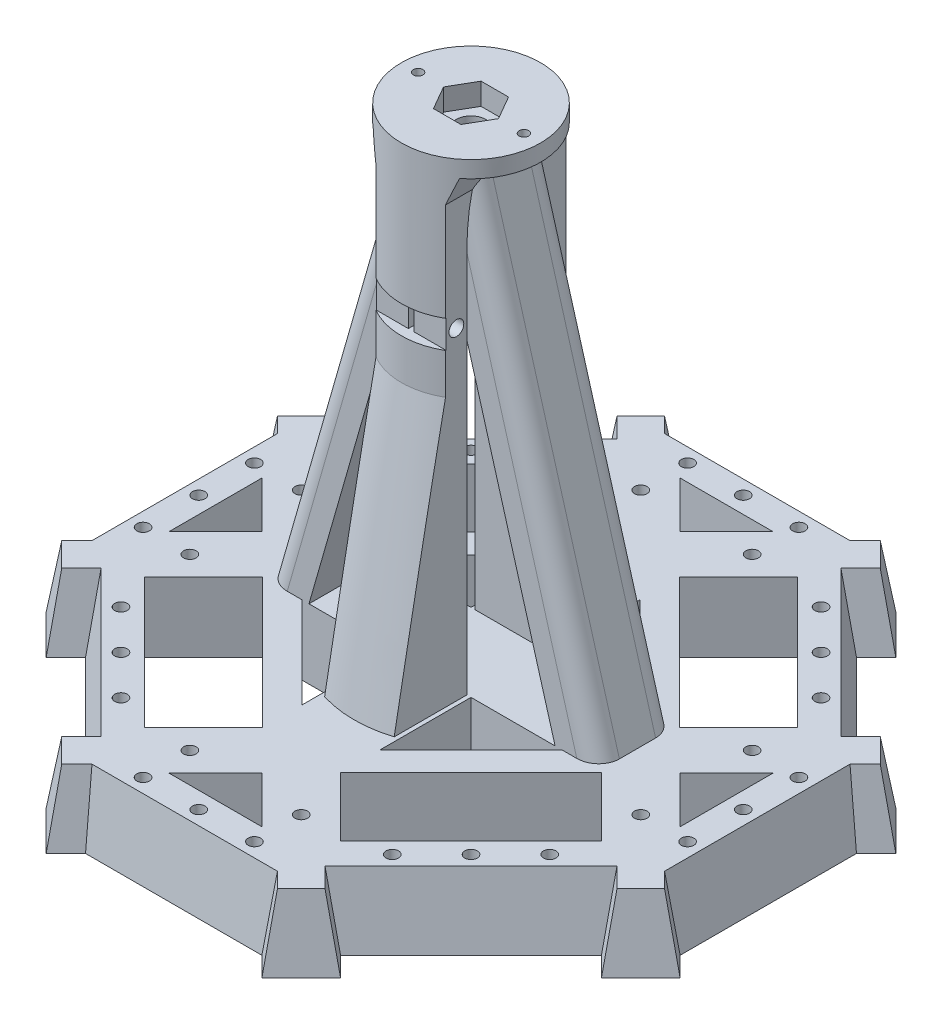
SolidWorks part; units mm, degrees
ref_plane "Front Plane" through (0, 0, 0) normal (0, 0, 1) x (1, 0, 0)
ref_plane "Top Plane" through (0, 0, 0) normal (0, 1, 0) x (1, 0, 0)
ref_plane "Right Plane" through (0, 0, 0) normal (1, 0, 0) x (0, 0, -1)
sketch "Sketch1" plane through (0, 0, 0) normal (0, 1, 0) x (1, 0, 0)
  line L0 (-1000, 0) -> (49000, 0) construction
  line L1 (-12.5, 29) -> (12.5, 29)
  line L2 (-12.5, 29) -> (-12.5, 14)
  line L3 (-12.5, 14) -> (12.5, 14)
  line L4 (12.5, 29) -> (12.5, 14)
  line L5 (-12.5, 29) -> (12.5, 14) construction
  line L6 (-12.5, 14) -> (12.5, 29) construction
  line L7 (-12.5, -14) -> (12.5, -29) construction
  line L8 (-12.5, -29) -> (12.5, -14) construction
  line L9 (12.5, -29) -> (12.5, -14)
  line L10 (-12.5, -14) -> (12.5, -14)
  line L11 (-12.5, -29) -> (-12.5, -14)
  line L12 (-12.5, -29) -> (12.5, -29)
  point P0 (0, 21.5)
  point P12 (0, -21.5)
  dimension "D1" = 25
  dimension "D2" = 15
  dimension "D3" = 14
extrude "Boss-Extrude1" add sketch "Sketch1" along normal blind 250
sketch "Sketch3" plane through (0, 0, 29) normal (0, 0, 1) x (1, 0, 0)
  line L0 (-12.5, 250) -> (-4.8, 276.4)
  line L1 (4.8, 276.4) -> (12.5, 250)
  line L2 (-12.5, 250) -> (12.5, 250) construction
  line L3 (-12.5, 250) -> (12.5, 250)
  arc A0 (4.8, 276.4) -> (-4.8, 276.4) centre (0, 275) ccw
  dimension "D1" = 10
  dimension "D2" = 25
extrude "Boss-Extrude2" add sketch "Sketch3" against normal up to surface (58 mm away) up to face at (0, 125, -29)
sketch "Sketch4" plane through (0, 250, 0) normal (0, -1, 0) x (1, 0, 0)
  line L1 (-12.5, 14) -> (12.5, 14)
  line L2 (-12.5, 14) -> (-12.5, -14)
  line L3 (-12.5, -14) -> (12.5, -14)
  line L4 (12.5, 14) -> (12.5, -14)
extrude "Cut-Extrude2" cut sketch "Sketch4" against normal through all
sketch "Sketch5" plane through (0, 0, -29) normal (0, 0, -1) x (-1, 0, 0)
  circle A1 centre (0, 275) radius 5
  dimension "D1" = 10
extrude "Boss-Extrude3" add sketch "Sketch5" against normal up to surface (58 mm away) up to face at (0, 176.0667, 29)
sketch "Sketch6" plane through (0, 0, 0) normal (0, -1, 0) x (1, 0, 0)
  line L1 (-12.5, -100) -> (12.5, -100)
  line L2 (-12.5, -100) -> (-12.5, 100)
  line L3 (-12.5, 100) -> (12.5, 100)
  line L4 (12.5, -100) -> (12.5, 100)
  line L5 (-12.5, -100) -> (12.5, 100) construction
  line L6 (-12.5, 100) -> (12.5, -100) construction
  point P0 (0, 0)
  dimension "D1" = 25
  dimension "D2" = 200
extrude "Boss-Extrude4" add sketch "Sketch6" along normal blind 25
sketch "Sketch7" plane through (0, 0, 0) normal (0, 1, 0) x (1, 0, 0)
  line L1 (-12.5, -14) -> (12.5, -14)
  line L2 (-12.5, -14) -> (-12.5, 14)
  line L3 (-12.5, 14) -> (12.5, 14)
  line L4 (12.5, -14) -> (12.5, 14)
extrude "Cut-Extrude3" cut sketch "Sketch7" along normal blind 323
sketch "Sketch12" plane through (0, 0, 0) normal (0, 1, 0) x (1, 0, 0)
  line L0 (-1000, 0) -> (49000, 0) construction
  line L1 (26.5, 39) -> (112.5, 39)
  line L4 (112.5, 39) -> (112.5, 14)
  line L5 (0, -1000) -> (0, 49000) construction
  line L6 (-12.5, 39) -> (-12.5, 14)
  line L7 (-26.5, 39) -> (-112.5, 39)
  line L8 (-112.5, 39) -> (-112.5, 14)
  line L9 (-26.5, 14) -> (-112.5, 14)
  line L10 (112.5, -39) -> (112.5, -14)
  line L13 (26.5, -39) -> (112.5, -39)
  line L14 (-26.5, -14) -> (-112.5, -14)
  line L15 (-112.5, -39) -> (-112.5, -14)
  line L16 (-26.5, -39) -> (-112.5, -39)
  line L17 (-12.5, -39) -> (-12.5, -14)
  line L18 (12.5, -75) -> (12.5, -100)
  line L21 (-12.5, 100) -> (12.5, 100) construction
  line L22 (12.5, 75) -> (12.5, 100) construction
  line L23 (-12.5, -100) -> (12.5, -100)
  line L24 (-12.5, -75) -> (-12.5, -100)
  line L25 (-12.5, -75) -> (12.5, -75)
  line L26 (-887.5, 26.5) -> (49112.5, 26.5) construction
  line L27 (-12.5, -14) -> (-12.5, 14) construction
  line L33 (-12.5, 14) -> (-12.5, 0)
  line L35 (-12.5, 53) -> (-12.5, 39)
  line L36 (-12.5, -100) -> (-12.5, -29) construction
  line L37 (-12.5, -53) -> (-12.5, -39)
  line L38 (12.5, -29) -> (12.5, -100) construction
  line L39 (12.5, 100) -> (12.5, 29) construction
  line L56 (12.5, 53) -> (12.5, 14)
  line L57 (112.5, 14) -> (12.5, 14)
  line L59 (112.5, -14) -> (12.5, -14)
  line L61 (12.5, -14) -> (12.5, -53)
  line L62 (-26.5, -14) -> (-12.5, -14)
  circle A0 centre (25, 26.5) radius 2.4
  circle A1 centre (37.5, 26.5) radius 2.4
  circle A2 centre (50, 26.5) radius 2.4
  circle A3 centre (62.5, 26.5) radius 2.4
  circle A4 centre (75, 26.5) radius 2.4
  circle A5 centre (87.5, 26.5) radius 2.4
  circle A6 centre (100, 26.5) radius 2.4
  circle A7 centre (100, -26.5) radius 2.4
  circle A8 centre (87.5, -26.5) radius 2.4
  circle A9 centre (75, -26.5) radius 2.4
  circle A10 centre (62.5, -26.5) radius 2.4
  circle A11 centre (50, -26.5) radius 2.4
  circle A12 centre (37.5, -26.5) radius 2.4
  circle A13 centre (25, -26.5) radius 2.4
  circle A14 centre (-100, 26.5) radius 2.4
  circle A15 centre (-87.5, 26.5) radius 2.4
  circle A16 centre (-75, 26.5) radius 2.4
  circle A17 centre (-62.5, 26.5) radius 2.4
  circle A18 centre (-50, 26.5) radius 2.4
  circle A19 centre (-37.5, 26.5) radius 2.4
  circle A20 centre (-25, 26.5) radius 2.4
  circle A21 centre (-25, -26.5) radius 2.4
  circle A22 centre (-37.5, -26.5) radius 2.4
  circle A23 centre (-50, -26.5) radius 2.4
  circle A24 centre (-62.5, -26.5) radius 2.4
  circle A25 centre (-75, -26.5) radius 2.4
  circle A26 centre (-87.5, -26.5) radius 2.4
  circle A27 centre (-100, -26.5) radius 2.4
  circle A28 centre (0, 90) radius 2.4
  circle A29 centre (0, 85) radius 2.4
  circle A30 centre (0, -90) radius 2.4
  circle A31 centre (0, -85) radius 2.4
  arc A35 (-26.5, 14) -> (-12.5, 0) centre (-26.5, 0) cw
  arc A36 (-26.5, 39) -> (-12.5, 53) centre (-26.5, 53) ccw
  arc A37 (-26.5, -39) -> (-12.5, -53) centre (-26.5, -53) cw
  arc A38 (12.5, -53) -> (26.5, -39) centre (26.5, -53) cw
  arc A39 (12.5, 53) -> (26.5, 39) centre (26.5, 53) ccw
  point P34 (112.5, 26.5)
  dimension "D5" = 4.8
  dimension "D8" = 12.5
  dimension "D9" = 4.8
  dimension "D10" = 4.8
  dimension "D11" = 10
  dimension "D14" = 14
  dimension "D15" = 14
  dimension "D16" = 14
  dimension "D17" = 14
  dimension "D18" = 14
  dimension "D1" = 25
  dimension "D3" = 61
  dimension "D4" = 25
  dimension "D7" = 7
extrude "Boss-Extrude7" add sketch "Sketch12" against normal up to surface (25 mm away) up to face at (0, -25, 0)
ref_plane "Plane1" through (-0.9497, -3.312, 0) normal (0.2756, 0.9613, 0) x (0, 0, -1)
sketch "Sketch14" plane through (-0.9497, -3.312, 0) normal (0.2756, 0.9613, 0) x (0, 0, -1)
  line L0 (14, 56.8936) -> (14, -12.0158) construction
  line L1 (-14, 57.5) -> (14, 57.5)
  line L2 (-14, 57.5) -> (-14, 42.5)
  line L3 (-14, 42.5) -> (14, 42.5)
  line L4 (14, 57.5) -> (14, 42.5)
  line L5 (-14, 57.5) -> (14, 42.5) construction
  line L6 (-14, 42.5) -> (14, 57.5) construction
  point P0 (0, 50)
  dimension "D1" = 28
  dimension "D2" = 15
  dimension "D3" = 50
sketch "Sketch16" plane through (0, 0, 0) normal (0, 1, 0) x (1, 0, 0)
  line L1 (12.5, -88.0748) -> (97.5, -39)
  line L2 (12.5, -70.7543) -> (67.5, -39)
  line L4 (12.5, -53) -> (12.5, -100) construction
  line L5 (-12.5, -70.7543) -> (-12.5, -88.0748)
  line L6 (26.5, -39) -> (112.5, -39) construction
  line L7 (112.5, -39) -> (112.5, -14) construction
  line L8 (-97.5, -39) -> (-67.5, -39)
  line L9 (97.5, -39) -> (67.5, -39)
  line L11 (12.5, -70.7543) -> (12.5, -88.0748)
  line L12 (-1000, 0) -> (49000, 0) construction
  line L13 (0, -1000) -> (0, 49000) construction
  line L14 (-834.739, -568.5682) -> (42466.5312, 24431.4318) construction
  line L15 (-12.5, -70.7543) -> (-67.5, -39)
  line L16 (-12.5, -88.0748) -> (-97.5, -39)
  line L17 (-12.5, 88.0748) -> (-97.5, 39)
  line L18 (-12.5, 70.7543) -> (-67.5, 39)
  line L19 (-97.5, 39) -> (-67.5, 39)
  line L20 (-12.5, 70.7543) -> (-12.5, 88.0748)
  line L21 (12.5, 70.7543) -> (12.5, 88.0748)
  line L22 (97.5, 39) -> (67.5, 39)
  line L23 (12.5, 70.7543) -> (67.5, 39)
  line L24 (12.5, 88.0748) -> (97.5, 39)
  circle A0 centre (25, -72.1976) radius 2.4
  circle A1 centre (37.5, -64.9808) radius 2.4
  circle A2 centre (50, -57.7639) radius 2.4
  circle A3 centre (75, -43.3301) radius 2.4
  circle A4 centre (62.5, -50.547) radius 2.4
  circle A5 centre (-62.5, -50.547) radius 2.4
  circle A6 centre (-75, -43.3301) radius 2.4
  circle A7 centre (-50, -57.7639) radius 2.4
  circle A8 centre (-37.5, -64.9808) radius 2.4
  circle A9 centre (-25, -72.1976) radius 2.4
  circle A10 centre (-25, 72.1976) radius 2.4
  circle A11 centre (-37.5, 64.9808) radius 2.4
  circle A12 centre (-50, 57.7639) radius 2.4
  circle A13 centre (-75, 43.3301) radius 2.4
  circle A14 centre (-62.5, 50.547) radius 2.4
  circle A15 centre (62.5, 50.547) radius 2.4
  circle A16 centre (75, 43.3301) radius 2.4
  circle A17 centre (50, 57.7639) radius 2.4
  circle A18 centre (37.5, 64.9808) radius 2.4
  circle A19 centre (25, 72.1976) radius 2.4
  point P16 (12.5, -79.4145)
  point P20 (25, -26.5)
  point P21 (50, -26.5)
  point P23 (62.5, -26.5)
  point P24 (75, -26.5)
  point P38 (37.5, -26.5)
  dimension "D1" = 4.8
  dimension "D2" = 30
  dimension "D3" = 15
extrude "Boss-Extrude13" add sketch "Sketch16" against normal up to surface (25 mm away) up to face at (-0.944, -25, -0.116)
extrude "Boss-Extrude14" add sketch "Sketch14" along normal blind 215 and the other way blind 48
mirror "Mirror1" about plane through (0, 0, 0) normal (1, 0, 0) of "Boss-Extrude14"
sketch "Sketch24" plane through (0, -25, 0) normal (0, -1, 0) x (1, 0, 0)
  line L1 (-207.1011, -152.3344) -> (207.1011, -152.3344)
  line L2 (-207.1011, -152.3344) -> (-207.1011, 152.3344)
  line L3 (-207.1011, 152.3344) -> (207.1011, 152.3344)
  line L4 (207.1011, -152.3344) -> (207.1011, 152.3344)
  line L5 (-207.1011, -152.3344) -> (207.1011, 152.3344) construction
  line L6 (-207.1011, 152.3344) -> (207.1011, -152.3344) construction
  point P0 (0, 0)
extrude "Cut-Extrude9" cut sketch "Sketch24" along normal blind 165
sketch "Sketch25" plane through (0, 0, -29) normal (0, 0, -1) x (-1, 0, 0)
  line L0 (-12.5, 0) -> (12.5, 0) construction
  line L1 (-74.6681, 165) -> (102.6778, 165)
  line L2 (-74.6681, 165) -> (-74.6681, 358.0748)
  line L3 (-74.6681, 358.0748) -> (102.6778, 358.0748)
  line L4 (102.6778, 165) -> (102.6778, 358.0748)
  dimension "D1" = 165
extrude "Cut-Extrude10" cut sketch "Sketch25" against normal through all both and the other way through all
sketch "Sketch26" plane through (0, 165, 0) normal (0, 1, 0) x (1, 0, 0)
  line L0 (-12.5, 29) -> (12.5, 29) construction
  line L1 (-29, 29) -> (29, 29)
  line L2 (-29, 29) -> (-29, -29)
  line L3 (-29, -29) -> (29, -29)
  line L4 (29, 29) -> (29, -29)
  line L5 (-29, 29) -> (29, -29) construction
  line L6 (-29, -29) -> (29, 29) construction
  point P0 (0, 0)
extrude "Boss-Extrude16" add sketch "Sketch26" along normal blind 6
sketch "Sketch29" plane through (0, 171, 0) normal (0, 1, 0) x (1, 0, 0)
  line L0 (0, -1000) -> (0, 49000) construction
  line L5 (-29, 29) -> (-29, -29) construction
  line L7 (20.5733, -2.725) -> (17.4267, -2.725)
  line L9 (-17.4267, -2.725) -> (-15.8534, 0)
  line L10 (-15.8534, 0) -> (-17.4267, 2.725)
  line L11 (-17.4267, 2.725) -> (-20.5733, 2.725)
  line L12 (-20.5733, 2.725) -> (-22.1466, 0)
  line L13 (-22.1466, 0) -> (-20.5733, -2.725)
  line L14 (-20.5733, -2.725) -> (-17.4267, -2.725)
  line L24 (22.1466, 0) -> (20.5733, -2.725)
  line L25 (20.5733, 2.725) -> (22.1466, 0)
  line L26 (17.4267, 2.725) -> (20.5733, 2.725)
  line L27 (15.8534, 0) -> (17.4267, 2.725)
  line L28 (17.4267, -2.725) -> (15.8534, 0)
  circle A0 centre (-19, 0) radius 2.725 construction
  circle A1 centre (19, 0) radius 2.725 construction
  circle A2 centre (19, 0) radius 1.7
  circle A4 centre (-19, 0) radius 1.7
  point P0 (0, 0)
  dimension "D6" = 3.4
  dimension "D1" = 10
  dimension "D2" = 5.45
sketch "Sketch30" plane through (0, 171, 0) normal (0, 1, 0) x (1, 0, 0)
  line L1 (4.9363, -8.55) -> (9.8727, 0)
  line L2 (9.8727, 0) -> (4.9363, 8.55)
  line L3 (4.9363, 8.55) -> (-4.9363, 8.55)
  line L4 (-4.9363, 8.55) -> (-9.8727, 0)
  line L5 (-9.8727, 0) -> (-4.9363, -8.55)
  line L6 (-4.9363, -8.55) -> (4.9363, -8.55)
  circle A0 centre (0, 0) radius 8.55 construction
  circle A1 centre (0, 0) radius 5.35
  dimension "D2" = 10.7
  dimension "D1" = 17.1
extrude "Cut-Extrude14" cut sketch "Sketch30" against normal blind 7.85 and the other way through all
extrude "Cut-Extrude15" cut sketch "Sketch30<2>" against normal blind 25 contours A1 region at (0, 171, 0)
sketch "Sketch30<2>" plane through (0, 171, 0) normal (0, 1, 0) x (1, 0, 0) same geometry as "Sketch30"
sketch "Sketch32" plane through (0, 171, 0) normal (0, 1, 0) x (1, 0, 0)
  line L1 (-29, -29) -> (29, -29)
  line L2 (-29, -29) -> (-29, 29)
  line L3 (-29, 29) -> (29, 29)
  line L4 (29, -29) -> (29, 29)
  circle A1 centre (0, 0) radius 25
  line M11 (29, -29) -> (29, 29)
  line M12 (29, 29) -> (-29, 29)
  line M13 (-29, 29) -> (-29, -29)
  line M14 (-29, -29) -> (29, -29)
  dimension "D1" = 50
extrude "Cut-Extrude16" cut sketch "Sketch32" against normal blind 15 contours A1 L2 M14 | A1 L1 M11 | A1 L4 M12 | A1 L3 M13 region at (-28.1798, 171, 0)
extrude "Cut-Extrude17" cut sketch "Sketch29" against normal blind 10 from offset 2.5 offset against normal yes
extrude "Cut-Extrude18" cut sketch "Sketch29<7>" against normal blind 10 contours A4 | A2 region at (19, 171, 0) region at (-19, 171, 0)
sketch "Sketch29<7>" plane through (0, 171, 0) normal (0, 1, 0) x (1, 0, 0) same geometry as "Sketch29"
chamfer "Chamfer1" distance 3 angle 71 2 edges at (12.5, 165, -17.8253) (-12.5, 165, -17.8253) first distance on face at (19, 165, 0) first distance on face at (-19, 165, 0)
sketch "Sketch34" plane through (0, 171, 0) normal (0, 1, 0) x (1, 0, 0)
  line L0 (-17.0747, 29) -> (19.0857, 29)
  line L1 (19.0857, 29) -> (17.3739, 17.9763)
  line L2 (-17.0747, 29) -> (-16.4279, 18.8448)
  line L3 (-15.6445, -19.5) -> (-15.6445, -31.0312)
  line L4 (-15.6445, -31.0312) -> (17.8974, -31.0312)
  line L5 (17.8974, -31.0312) -> (17.8974, -17.4551)
  circle A0 centre (0, 0) radius 25 construction
  arc A1 (-16.4279, 18.8448) -> (17.3739, 17.9763) centre (0, 0) cw
  arc A2 (-15.6445, -19.5) -> (17.8974, -17.4551) centre (0, 0) ccw
extrude "Cut-Extrude19" cut sketch "Sketch34" against normal up to surface (171 mm away) up to face at (29.0251, 0, -49.7137)
sketch "Sketch35" plane through (0, 0, 14) normal (0, 0, 1) x (1, 0, 0)
  line L0 (-12.5, 156.2874) -> (-12.5, 0) construction
  line L1 (-12.5, 121) -> (12.5, 121)
  line L2 (-12.5, 121) -> (-12.5, 111)
  line L3 (-12.5, 111) -> (12.5, 111)
  line L4 (12.5, 121) -> (12.5, 111)
  line L5 (0, 111) -> (0, 121) construction
  line L6 (-12.5, 116) -> (12.5, 116) construction
  line L7 (12.5, 0) -> (12.5, 156.2874) construction
  line L8 (25, 171) -> (-25, 171) construction
  line L9 (-1, 121) -> (-1, 111)
  line L10 (1, 121) -> (1, 111)
  point P912 (0, 116)
  line M5 (12.5, 156.2874) -> (12.5, 110.5954)
  dimension "D1" = 50
  dimension "D2" = 10
  dimension "D3" = 1
  dimension "D4" = 1
chamfer "Chamfer2" distance 17 angle 80 2 edges at (0, 0, -25) (0, 0, 25) first distance on face at (-1.0261, 0, -30.1609) first distance on face at (0, 0, 38.3778)
fillet "Fillet1" radius 7.5 4 edges at (36.8413, 80.1264, -14) (36.8413, 80.1264, 14) (-36.8413, 80.1264, -14) (-36.8413, 80.1264, 14)
extrude "Cut-Extrude21" cut sketch "Sketch35" along normal blind 27 from offset 7.5 contours L9 L1 L2 L3 | L10 L1 L9 L3 | L1 L10 L3 M5 region at (-6.75, 116, 14) region at (0, 116, 14) region at (6.75, 116, 14)
extrude "Cut-Extrude23" cut sketch "Sketch35<3>" along normal blind 27 contours L10 L1 L9 L3 region at (0, 116, 14)
sketch "Sketch35<3>" plane through (0, 0, 14) normal (0, 0, 1) x (1, 0, 0) same geometry as "Sketch35"
sketch "Sketch36" plane through (12.5, 0, 0) normal (1, 0, 0) x (0, 0, -1)
  line L0 (-14, 137.8051) -> (-14, 110.5954) construction
  line L1 (-14, 121) -> (-21.5, 121) construction
  line L2 (-14, 121) -> (-14, 111) construction
  line L3 (-14, 111) -> (-21.5, 111) construction
  line L4 (-21.5, 121) -> (-21.5, 111) construction
  line L5 (-14, 121) -> (-21.5, 111) construction
  line L6 (-14, 111) -> (-21.5, 121) construction
  line L7 (-25, 121) -> (-21.6506, 121) construction
  circle A0 centre (-17.75, 116) radius 1.7
  point P0 (-17.75, 116)
  dimension "D1" = 3.4
extrude "Cut-Extrude24" cut sketch "Sketch36" against normal blind 27
sketch "Sketch38" plane through (-12.5, 0, 0) normal (-1, 0, 0) x (0, 0, 1)
  line L1 (15.025, 114.4267) -> (17.75, 112.8534)
  line L2 (17.75, 112.8534) -> (20.475, 114.4267)
  line L3 (20.475, 114.4267) -> (20.475, 117.5733)
  line L4 (20.475, 117.5733) -> (17.75, 119.1466)
  line L5 (17.75, 119.1466) -> (15.025, 117.5733)
  line L6 (15.025, 117.5733) -> (15.025, 114.4267)
  circle A0 centre (17.75, 116) radius 2.725 construction
  dimension "D1" = 5.45
extrude "Cut-Extrude25" cut sketch "Sketch38" against normal blind 6.5
sketch "Sketch39" plane through (12.5, 0, 0) normal (1, 0, 0) x (0, 0, -1)
  circle A0 centre (-17.75, 116) radius 2.65
  dimension "D1" = 5.3
extrude "Cut-Extrude26" cut sketch "Sketch39" against normal blind 8
sketch "Sketch40" plane through (0, 0, 0) normal (0, 1, 0) x (1, 0, 0)
  line L0 (66.9859, -14) -> (66.9859, 14) construction
  line L1 (-66.9859, -14) -> (66.9859, -14)
  line L2 (-66.9859, -14) -> (-66.9859, 14)
  line L3 (-66.9859, 14) -> (66.9859, 14)
  line L4 (66.9859, -14) -> (66.9859, 14)
  line L5 (-66.9859, -14) -> (66.9859, 14) construction
  line L6 (-66.9859, 14) -> (66.9859, -14) construction
  line L8 (-12.5, -14) -> (-44.2127, -14) construction
  line L9 (-136.0522, -108.7903) -> (136.0522, -108.7903)
  line L10 (-136.0522, -108.7903) -> (-136.0522, 108.7903)
  line L11 (-136.0522, 108.7903) -> (136.0522, 108.7903)
  line L12 (136.0522, -108.7903) -> (136.0522, 108.7903)
  line L13 (-136.0522, -108.7903) -> (136.0522, 108.7903) construction
  line L14 (-136.0522, 108.7903) -> (136.0522, -108.7903) construction
  point P0 (0, 0)
  point P10 (0, 0)
extrude "Cut-Extrude29" cut sketch "Sketch40" against normal blind 65 contours L9 L12 L11 L10 L4 L1 L2 L3 region at (-132.5682, 0, 0)
sketch "Sketch41" plane through (0, 0, -14) normal (0, 0, -1) x (-1, 0, 0)
  line L1 (29.8998, 0) -> (-27.6085, 0)
  line L2 (29.8998, 0) -> (29.8998, -25.9275)
  line L3 (29.8998, -25.9275) -> (-27.6085, -25.9275)
  line L4 (-27.6085, 0) -> (-27.6085, -25.9275)
  line L5 (1.1457, -25.9275) -> (1.1457, 0) construction
  line L6 (29.8998, -12.9637) -> (-27.6085, -12.9637) construction
  point P612 (1.1457, -12.9637)
extrude "Cut-Extrude30" cut sketch "Sketch41" against normal blind 65
sketch "Sketch42" plane through (0, 0, 0) normal (0, -1, 0) x (1, 0, 0)
  line L0 (51.3814, -14) -> (66.9859, -14) construction
  line L1 (-75, -75) -> (75, -75)
  line L2 (-75, -75) -> (-75, -14)
  line L3 (-75, -14) -> (-12.5, -14)
  line L4 (75, -75) -> (75, -14)
  line L5 (-75, -75) -> (75, -14) construction
  line L6 (-75, -14) -> (75, -75) construction
  line L7 (51.3814, 14) -> (66.9859, 14) construction
  line L8 (-75, 75) -> (75, 75)
  line L9 (-75, 75) -> (-75, 14)
  line L10 (-75, 14) -> (-12.5, 14)
  line L11 (75, 75) -> (75, 14)
  line L12 (-75, 75) -> (75, 14) construction
  line L13 (-75, 14) -> (75, 75) construction
  line L14 (12.5, 14) -> (12.5, 40.0968) construction
  line L16 (-12.5, -14) -> (-12.5, 14)
  line L18 (12.5, -14) -> (12.5, 14)
  line L19 (-12.5, -14) -> (12.5, 14) construction
  line L20 (-12.5, 14) -> (12.5, -14) construction
  line L21 (12.5, 14) -> (75, 14)
  line L22 (12.5, -14) -> (75, -14)
  point P0 (0, -44.5)
  point P7 (0, 44.5)
  point P14 (0, 0)
  dimension "D1" = 150
  dimension "D2" = 150
  dimension "D3" = 150
extrude "Boss-Extrude20" add sketch "Sketch42" along normal up to surface (25 mm away) up to face at (59.1836, -25, 0)
sketch "Sketch43" plane through (0, 0, 0) normal (0, 1, 0) x (1, 0, 0)
  line L0 (-75, 14) -> (-75, -14)
  line L1 (-12.5, -14) -> (-75, -14)
  line L2 (-12.5, -14) -> (-12.5, -75)
  line L3 (-12.5, -75) -> (-75, -75)
  line L4 (-75, -14) -> (-75, -75)
  line L5 (-43.75, -75) -> (-43.75, -14) construction
  line L6 (-12.5, -44.5) -> (-75, -44.5) construction
  line L7 (75, -75) -> (12.5, -75)
  line L8 (75, -75) -> (75, -14)
  line L9 (75, -14) -> (12.5, -14)
  line L10 (12.5, -75) -> (12.5, -14)
  line L11 (43.75, -14) -> (43.75, -75) construction
  line L12 (75, -44.5) -> (12.5, -44.5) construction
  line L13 (12.5, 14) -> (75, 14)
  line L14 (12.5, 14) -> (12.5, 75)
  line L15 (12.5, 75) -> (75, 75)
  line L16 (75, 14) -> (75, 75)
  line L17 (43.75, 75) -> (43.75, 14) construction
  line L18 (12.5, 44.5) -> (75, 44.5) construction
  line L19 (-12.5, 14) -> (-75, 14)
  line L20 (-12.5, 14) -> (-12.5, 75)
  line L21 (-12.5, 75) -> (-75, 75)
  line L22 (-75, 14) -> (-75, 75)
  line L23 (-43.75, 75) -> (-43.75, 14) construction
  line L24 (-12.5, 44.5) -> (-75, 44.5) construction
  line L29 (-59.8172, 14) -> (-59.8172, -14)
  line L31 (59.8172, -14) -> (59.8172, 14)
  line L32 (75, -14) -> (75, 14)
  point P288 (-43.75, -44.5)
  point P311 (-43.75, 44.5)
  point P363 (43.75, 44.5)
  point P727 (43.75, -44.5)
  line M17 (-59.8172, -6.5) -> (-59.8172, -14)
  line M18 (-59.8172, -14) -> (-75, -14)
  line M19 (-75, -14) -> (-75, -75)
  line M20 (-75, -75) -> (75, -75)
  line M21 (75, -75) -> (75, -14)
  line M22 (75, -14) -> (59.8172, -14)
  line M23 (59.8172, -14) -> (59.8172, -6.5)
  line M25 (52.015, -14) -> (44.2127, -14)
  line M26 (44.2127, -14) -> (12.5, -14)
  line M27 (12.5, -14) -> (12.5, -40.0968)
  line M29 (-12.5, -40.0968) -> (-12.5, -14)
  line M30 (-12.5, -14) -> (-44.2127, -14)
  line M31 (-44.2127, -14) -> (-52.015, -14)
extrude "Cut-Extrude32" cut sketch "Sketch43" against normal blind 65 contours L2 L1 M29 M30 M31 M18 M19 M20 | L10 L9 M20 M21 M22 M25 M26 M27 | L13 L16 L15 L14 | L22 L19 L20 L21 region at (-43.75, 0, -44.5) region at (43.75, 0, 44.5) region at (-43.75, 0, 44.5) region at (43.75, 0, -44.5)
extrude "Boss-Extrude21" add sketch "Sketch43<4>" along direction (0, 1, 0) on the side against the normal up to surface (25 mm away) contours L29 L19 L0 M18 M17 | L32 L13 L31 M22 M23 region at (-67.4086, 0, 0) region at (67.4086, 0, 0) up to face at (59.1836, -25, 0)
sketch "Sketch43<4>" plane through (0, 0, 0) normal (0, 1, 0) x (1, 0, 0) same geometry as "Sketch43"
sketch "Sketch44" plane through (0, 0, 0) normal (0, 1, 0) x (1, 0, 0)
  line L0 (12.5, -75) -> (-12.5, -75) construction
  line L1 (-14, 75) -> (14, 75)
  line L2 (-14, 75) -> (-14, 14)
  line L3 (-14, -75) -> (14, -75)
  line L4 (14, 75) -> (14, 14)
  line L5 (-14, 75) -> (14, -75) construction
  line L6 (-14, -75) -> (14, 75) construction
  line L7 (52.015, 14) -> (75, 14) construction
  line L8 (-75, -14) -> (-14, -14)
  line L9 (-75, -14) -> (-75, 14)
  line L10 (-75, 14) -> (-14, 14)
  line L11 (75, -14) -> (75, 14)
  line L12 (0, 10.0823) -> (0, -17.9177) construction
  line L13 (-75, 0) -> (75, 0) construction
  line L14 (-14, -14) -> (-14, -75)
  line L15 (-52.015, 14) -> (-75, 14) construction
  line L16 (14, -14) -> (75, -14)
  line L17 (14, -14) -> (14, -75)
  line L18 (14, 14) -> (75, 14)
  point P0 (0, 0)
  point P368 (0, 0)
  dimension "D1" = 28
extrude "Boss-Extrude22" add sketch "Sketch44" against normal up to surface (25 mm away) up to face at (0, -25, 0)
sketch "Sketch45" plane through (0, 0, 0) normal (0, 1, 0) x (1, 0, 0)
  line L0 (52.015, 14) -> (75, 14) construction
  line L1 (25.5966, 86.5966) -> (35380.9357, 35441.9357) construction
  line L2 (-12.2492, 73.2492) -> (-32135.779, 32196.779) construction
  line L3 (-52.015, 14) -> (-12.5, 14) construction
  line L4 (113.8909, -38.7487) -> (75, 0.1421)
  line L5 (14, 14) -> (14, 75) construction
  line L6 (38.7487, 113.8909) -> (-0.1421, 75)
  line L7 (38.7487, 113.8909) -> (52.8909, 99.7487)
  line L8 (-0.1421, 75) -> (14, 60.8579)
  line L9 (52.8909, 99.7487) -> (14, 60.8579)
  line L10 (38.7487, 113.8909) -> (14, 60.8579) construction
  line L11 (-0.1421, 75) -> (52.8909, 99.7487) construction
  line L12 (0, -1000) -> (0, 49000) construction
  line L13 (0.1421, 75) -> (-52.8909, 99.7487) construction
  line L14 (-38.7487, 113.8909) -> (-14, 60.8579) construction
  line L15 (-52.8909, 99.7487) -> (-14, 60.8579)
  line L16 (0.1421, 75) -> (-14, 60.8579)
  line L17 (-38.7487, 113.8909) -> (-52.8909, 99.7487)
  line L18 (-38.7487, 113.8909) -> (0.1421, 75)
  line L19 (113.8909, -38.7487) -> (99.7487, -52.8909)
  line L20 (75, 0.1421) -> (60.8579, -14)
  line L21 (99.7487, -52.8909) -> (60.8579, -14)
  line L22 (99.7487, 52.8909) -> (60.8579, 14)
  line L23 (75, -0.1421) -> (60.8579, 14)
  line L24 (113.8909, 38.7487) -> (99.7487, 52.8909)
  line L25 (113.8909, 38.7487) -> (75, -0.1421)
  line L26 (113.8909, -38.7487) -> (60.8579, -14) construction
  line L27 (75, 0.1421) -> (99.7487, -52.8909) construction
  line L28 (75, -0.1421) -> (99.7487, 52.8909) construction
  line L29 (113.8909, 38.7487) -> (60.8579, 14) construction
  line L30 (-38.7487, -113.8909) -> (0.1421, -75)
  line L31 (-38.7487, -113.8909) -> (-52.8909, -99.7487)
  line L32 (0.1421, -75) -> (-14, -60.8579)
  line L33 (-52.8909, -99.7487) -> (-14, -60.8579)
  line L34 (52.8909, -99.7487) -> (14, -60.8579)
  line L35 (-0.1421, -75) -> (14, -60.8579)
  line L36 (38.7487, -113.8909) -> (52.8909, -99.7487)
  line L37 (38.7487, -113.8909) -> (-0.1421, -75)
  line L38 (-38.7487, -113.8909) -> (-14, -60.8579) construction
  line L39 (0.1421, -75) -> (-52.8909, -99.7487) construction
  line L40 (-0.1421, -75) -> (52.8909, -99.7487) construction
  line L41 (38.7487, -113.8909) -> (14, -60.8579) construction
  line L42 (-113.8909, 38.7487) -> (-75, -0.1421)
  line L43 (-113.8909, 38.7487) -> (-99.7487, 52.8909)
  line L44 (-75, -0.1421) -> (-60.8579, 14)
  line L45 (-99.7487, 52.8909) -> (-60.8579, 14)
  line L46 (-99.7487, -52.8909) -> (-60.8579, -14)
  line L47 (-75, 0.1421) -> (-60.8579, -14)
  line L48 (-113.8909, -38.7487) -> (-99.7487, -52.8909)
  line L49 (-113.8909, -38.7487) -> (-75, 0.1421)
  line L50 (-113.8909, 38.7487) -> (-60.8579, 14) construction
  line L51 (-75, -0.1421) -> (-99.7487, 52.8909) construction
  line L52 (-75, 0.1421) -> (-99.7487, -52.8909) construction
  line L53 (-113.8909, -38.7487) -> (-60.8579, -14) construction
  point P9 (26.3744, 87.3744)
  point P19 (-26.3744, 87.3744)
  point P29 (87.3744, -26.3744)
  point P37 (87.3744, 26.3744)
  point P39 (-26.3744, -87.3744)
  point P47 (26.3744, -87.3744)
  point P49 (-87.3744, 26.3744)
  point P57 (-87.3744, -26.3744)
  point P58 (0, 0)
  line M9 (14, 75) -> (-14, 75)
  line M10 (-14, 75) -> (-14, 14)
  line M14 (-14, -14) -> (-14, -75)
  line M15 (-14, -75) -> (14, -75)
  line M16 (14, -75) -> (14, -14)
  line M20 (14, 14) -> (14, 75)
  dimension "D1" = 45
  dimension "D2" = 45
  dimension "D3" = 20
  dimension "D4" = 55
  dimension "D5" = 4
extrude "Boss-Extrude23" add sketch "Sketch45" along direction (0, 1, 0) on the side against the normal up to surface (25 mm away) contours L42 L49 L47 L44 L45 L43 | L49 L48 L46 L47 L44 L42 | L30 L37 L33 L31 M15 M14 | L37 L36 L34 L30 M16 M15 | L4 L25 L23 L20 L21 L19 | L25 L24 L22 L23 L20 L4 | L6 L18 L9 L7 M9 M20 | L18 L17 L15 L6 M10 M9 | L18 L6 M9 | L49 L42 L44 L47 | L37 L30 M15 | L25 L4 L20 L23 region at (87.3748, 0, 26.3753) region at (75, 0, 0) region at (87.3748, 0, -26.3753) region at (28.0838, 0, -89.0835) region at (0, 0, -75.0474) region at (-28.0838, 0, -89.0835) region at (-28.0838, 0, 89.0835) region at (0, 0, 75.0474) region at (28.0838, 0, 89.0835) region at (-87.3748, 0, -26.3753) region at (-75, 0, 0) region at (-87.3748, 0, 26.3753) up to face at (0, -25, 0)
sketch "Sketch46" plane through (0, 0, 0) normal (0, 1, 0) x (1, 0, 0)
  line L0 (-60.8579, 14) -> (-53.7868, 6.9289)
  line L1 (-60.8579, 14) -> (-14, 60.8579)
  line L2 (-53.7868, 6.9289) -> (-6.9289, 53.7868)
  line L3 (-14, 60.8579) -> (-6.9289, 53.7868)
  line L4 (-99.7487, 52.8909) -> (-60.8579, 14) construction
  line L5 (-52.8909, 99.7487) -> (-14, 60.8579) construction
  line L6 (-92.6777, 45.8198) -> (-82.0711, 35.2132)
  line L7 (-92.6777, 45.8198) -> (-45.8198, 92.6777)
  line L8 (-82.0711, 35.2132) -> (-35.2132, 82.0711)
  line L9 (-45.8198, 92.6777) -> (-35.2132, 82.0711)
  line L10 (-38.7487, 113.8909) -> (-52.8909, 99.7487) construction
  line L11 (45.8198, 92.6777) -> (35.2132, 82.0711)
  line L12 (45.8198, 92.6777) -> (92.6777, 45.8198)
  line L13 (92.6777, 45.8198) -> (82.0711, 35.2132)
  line L14 (35.2132, 82.0711) -> (82.0711, 35.2132)
  line L15 (14, 60.8579) -> (6.9289, 53.7868)
  line L16 (14, 60.8579) -> (60.8579, 14)
  line L17 (60.8579, 14) -> (53.7868, 6.9289)
  line L18 (6.9289, 53.7868) -> (53.7868, 6.9289)
  line L19 (92.6777, -45.8198) -> (82.0711, -35.2132)
  line L20 (92.6777, -45.8198) -> (45.8198, -92.6777)
  line L21 (45.8198, -92.6777) -> (35.2132, -82.0711)
  line L22 (82.0711, -35.2132) -> (35.2132, -82.0711)
  line L23 (60.8579, -14) -> (53.7868, -6.9289)
  line L24 (60.8579, -14) -> (14, -60.8579)
  line L25 (14, -60.8579) -> (6.9289, -53.7868)
  line L26 (53.7868, -6.9289) -> (6.9289, -53.7868)
  line L27 (-45.8198, -92.6777) -> (-35.2132, -82.0711)
  line L28 (-45.8198, -92.6777) -> (-92.6777, -45.8198)
  line L29 (-92.6777, -45.8198) -> (-82.0711, -35.2132)
  line L30 (-35.2132, -82.0711) -> (-82.0711, -35.2132)
  line L31 (-14, -60.8579) -> (-6.9289, -53.7868)
  line L32 (-14, -60.8579) -> (-60.8579, -14)
  line L33 (-60.8579, -14) -> (-53.7868, -6.9289)
  line L34 (-6.9289, -53.7868) -> (-53.7868, -6.9289)
  line L35 (-92.6777, 45.8198) -> (-106.8198, 31.6777) construction
  line L36 (-113.8909, 38.7487) -> (-75.1421, 0) construction
  line L37 (-82.0711, 35.2132) -> (-99.7487, 24.6066) construction
  line L38 (-113.8909, -38.7487) -> (-75.1421, 0) construction
  line L39 (-106.8198, 31.6777) -> (-91.8198, 31.6777)
  line L40 (-106.8198, 31.6777) -> (-106.8198, -31.6777)
  line L41 (-106.8198, -31.6777) -> (-91.8198, -31.6777)
  line L42 (-91.8198, 31.6777) -> (-91.8198, -31.6777)
  line L43 (-99.3198, -31.6777) -> (-99.3198, 31.6777) construction
  line L44 (-106.8198, 0) -> (-91.8198, 0) construction
  line L45 (-113.8909, 38.7487) -> (-99.7487, 52.8909) construction
  line L46 (31.6777, 106.8198) -> (-31.6777, 106.8198)
  line L47 (31.6777, 106.8198) -> (31.6777, 91.8198)
  line L48 (31.6777, 91.8198) -> (-31.6777, 91.8198)
  line L49 (-31.6777, 106.8198) -> (-31.6777, 91.8198)
  line L50 (106.8198, -31.6777) -> (106.8198, 31.6777)
  line L51 (106.8198, -31.6777) -> (91.8198, -31.6777)
  line L52 (91.8198, -31.6777) -> (91.8198, 31.6777)
  line L53 (106.8198, 31.6777) -> (91.8198, 31.6777)
  line L54 (-31.6777, -106.8198) -> (31.6777, -106.8198)
  line L55 (-31.6777, -106.8198) -> (-31.6777, -91.8198)
  line L56 (-31.6777, -91.8198) -> (31.6777, -91.8198)
  line L57 (31.6777, -106.8198) -> (31.6777, -91.8198)
  point P42 (0, 0)
  point P67 (0, 0)
  point P2600 (-99.3198, 0)
  line M6 (-60.8579, 14) -> (-99.7487, 52.8909)
  line M8 (-113.8909, 38.7487) -> (-75.1421, 0)
  line M9 (-75.1421, 0) -> (-113.8909, -38.7487)
  line M11 (-99.7487, -52.8909) -> (-60.8579, -14)
  dimension "D1" = 10
  dimension "D2" = 15
  dimension "D3" = 10
  dimension "D5" = 15
  dimension "D4" = 4
  dimension "D6" = 4
extrude "Boss-Extrude24" add sketch "Sketch46" against normal up to surface (25 mm away) contours L9 L7 L8 M6 | L3 L1 L2 M6 | L15 L18 L17 L16 | L11 L14 L13 L12 | L23 L26 L25 L24 | L19 L22 L21 L20 | L31 L34 L32 M11 | L27 L30 L28 M11 region at (-33.8934, 0, -33.8934) region at (-63.9454, 0, -63.9454) region at (63.9454, 0, -63.9454) region at (33.8934, 0, -33.8934) region at (63.9454, 0, 63.9454) region at (33.8934, 0, 33.8934) region at (-63.9454, 0, 63.9454) region at (-33.8934, 0, 33.8934) up to face at (0, -25, 0)
extrude "Boss-Extrude25" add sketch "Sketch46<3>" along direction (0, 1, 0) on the side against the normal up to surface (25 mm away) contours L42 L40 M8 M9 | L46 L49 L48 L47 | L50 L53 L52 L51 | L54 L57 L56 L55 region at (-100.0953, 0, 0) region at (0, 0, -99.3198) region at (99.3198, 0, 0) region at (0, 0, 99.3198) up to face at (0, -25, 0)
sketch "Sketch46<3>" plane through (0, 0, 0) normal (0, 1, 0) x (1, 0, 0) same geometry as "Sketch46"
chamfer "Chamfer3" distance 25 angle 9 32 edges at (-45.8198, 0, 106.8198) (-49.3553, 0, 96.2132) (-69.2487, 0, 69.2487) (-96.2132, 0, 49.3553) (-106.8198, 0, 45.8198) (-110.3553, 0, 35.2132) (-106.8198, 0, 0) (-110.3553, 0, -35.2132) (-106.8198, 0, -45.8198) (-96.2132, 0, -49.3553) (-69.2487, 0, -69.2487) (-49.3553, 0, -96.2132) (-45.8198, 0, -106.8198) (-35.2132, 0, -110.3553) (0, 0, -106.8198) (35.2132, 0, -110.3553) (45.8198, 0, -106.8198) (49.3553, 0, -96.2132) (69.2487, 0, -69.2487) (96.2132, 0, -49.3553) (106.8198, 0, -45.8198) (110.3553, 0, -35.2132) (106.8198, 0, 0) (110.3553, 0, 35.2132) (106.8198, 0, 45.8198) (96.2132, 0, 49.3553) (69.2487, 0, 69.2487) (49.3553, 0, 96.2132) (45.8198, 0, 106.8198) (35.2132, 0, 110.3553) (0, 0, 106.8198) (-35.2132, 0, 110.3553) first distance on face at (-45.8198, -12.5, 106.8198) first distance on face at (-49.3553, -12.5, 96.2132) first distance on face at (-69.2487, -12.5, 69.2487) first distance on face at (-96.2132, -12.5, 49.3553) first distance on face at (-106.8198, -12.5, 45.8198) first distance on face at (-110.3553, -12.5, 35.2132) first distance on face at (-106.8198, -12.5, 0) first distance on face at (-110.3553, -12.5, -35.2132) first distance on face at (-106.8198, -12.5, -45.8198) first distance on face at (-96.2132, -12.5, -49.3553) first distance on face at (-69.2487, -12.5, -69.2487) first distance on face at (-49.3553, -12.5, -96.2132) first distance on face at (-45.8198, -12.5, -106.8198) first distance on face at (-35.2132, -12.5, -110.3553) first distance on face at (0, -12.5, -106.8198) first distance on face at (35.2132, -12.5, -110.3553) first distance on face at (45.8198, -12.5, -106.8198) first distance on face at (49.3553, -12.5, -96.2132) first distance on face at (69.2487, -12.5, -69.2487) first distance on face at (96.2132, -12.5, -49.3553) first distance on face at (106.8198, -12.5, -45.8198) first distance on face at (110.3553, -12.5, -35.2132) first distance on face at (106.8198, -12.5, 0) first distance on face at (110.3553, -12.5, 35.2132) first distance on face at (106.8198, -12.5, 45.8198) first distance on face at (96.2132, -12.5, 49.3553) first distance on face at (69.2487, -12.5, 69.2487) first distance on face at (49.3553, -12.5, 96.2132) first distance on face at (45.8198, -12.5, 106.8198) first distance on face at (35.2132, -12.5, 110.3553) first distance on face at (0, -12.5, 106.8198) first distance on face at (-35.2132, -12.5, 110.3553)
sketch "Sketch48" plane through (0, 0, 0) normal (0, 1, 0) x (1, 0, 0)
  line L0 (0, -1000) -> (0, 49000) construction
  line L1 (16.6777, 91.8198) -> (-16.6777, 91.8198) construction
  line L2 (705.637, -644.637) -> (-34649.7012, 34710.7012) construction
  line L3 (-705.4833, -644.4833) -> (34649.8557, 34710.8557) construction
  line L4 (-707.1068, -707.1068) -> (34648.2323, 34648.2323) construction
  line L5 (-16.6777, 91.8198) -> (0, 75.1421) construction
  line L6 (12.5, 14) -> (52.015, 14) construction
  line L7 (16.6777, 91.8198) -> (0, 75.1421) construction
  line L8 (35.2132, 82.0711) -> (82.0711, 35.2132) construction
  circle A0 centre (0, 97.8198) radius 2.25
  circle A1 centre (20, 97.8198) radius 2.25
  circle A4 centre (-20, 97.8198) radius 2.25
  circle A8 centre (20, 81) radius 2.25
  circle A9 centre (-20, 81) radius 2.25
  circle A12 centre (97.8198, 0) radius 2.25
  circle A13 centre (97.8198, -20) radius 2.25
  circle A14 centre (97.8198, 20) radius 2.25
  circle A15 centre (81, -20) radius 2.25
  circle A16 centre (81, 20) radius 2.25
  circle A17 centre (0, -97.8198) radius 2.25
  circle A18 centre (-20, -97.8198) radius 2.25
  circle A19 centre (20, -97.8198) radius 2.25
  circle A20 centre (-20, -81) radius 2.25
  circle A21 centre (20, -81) radius 2.25
  circle A22 centre (-97.8198, 0) radius 2.25
  circle A23 centre (-97.8198, 20) radius 2.25
  circle A24 centre (-97.8198, -20) radius 2.25
  circle A25 centre (-81, 20) radius 2.25
  circle A26 centre (-81, -20) radius 2.25
  circle A27 centre (62.8848, 62.8848) radius 2.25
  circle A28 centre (77.0269, 48.7426) radius 2.25
  circle A29 centre (48.7426, 77.0269) radius 2.25
  circle A30 centre (62.8848, -62.8848) radius 2.25
  circle A31 centre (48.7426, -77.0269) radius 2.25
  circle A32 centre (77.0269, -48.7426) radius 2.25
  circle A33 centre (-62.8848, -62.8848) radius 2.25
  circle A34 centre (-77.0269, -48.7426) radius 2.25
  circle A35 centre (-48.7426, -77.0269) radius 2.25
  circle A36 centre (-62.8848, 62.8848) radius 2.25
  circle A37 centre (-48.7426, 77.0269) radius 2.25
  circle A38 centre (-77.0269, 48.7426) radius 2.25
  point P56 (0, 0)
  point P88 (0, 0)
  dimension "D1" = 4.5
  dimension "D2" = 6
  dimension "D5" = 20
  dimension "D8" = 20
  dimension "D9" = 4
  dimension "D10" = 135
  dimension "D11" = 4.5
  dimension "D12" = 4.5
  dimension "D13" = 4.5
  dimension "D14" = 6
  dimension "D17" = 20
  dimension "D18" = 20
  dimension "D6" = 10
  dimension "D7" = 10
  dimension "D3" = 2
  dimension "D4" = 2
  dimension "D15" = 2
  dimension "D16" = 2
  dimension "D19" = 4
extrude "Cut-Extrude34" cut sketch "Sketch48" against normal blind 65
